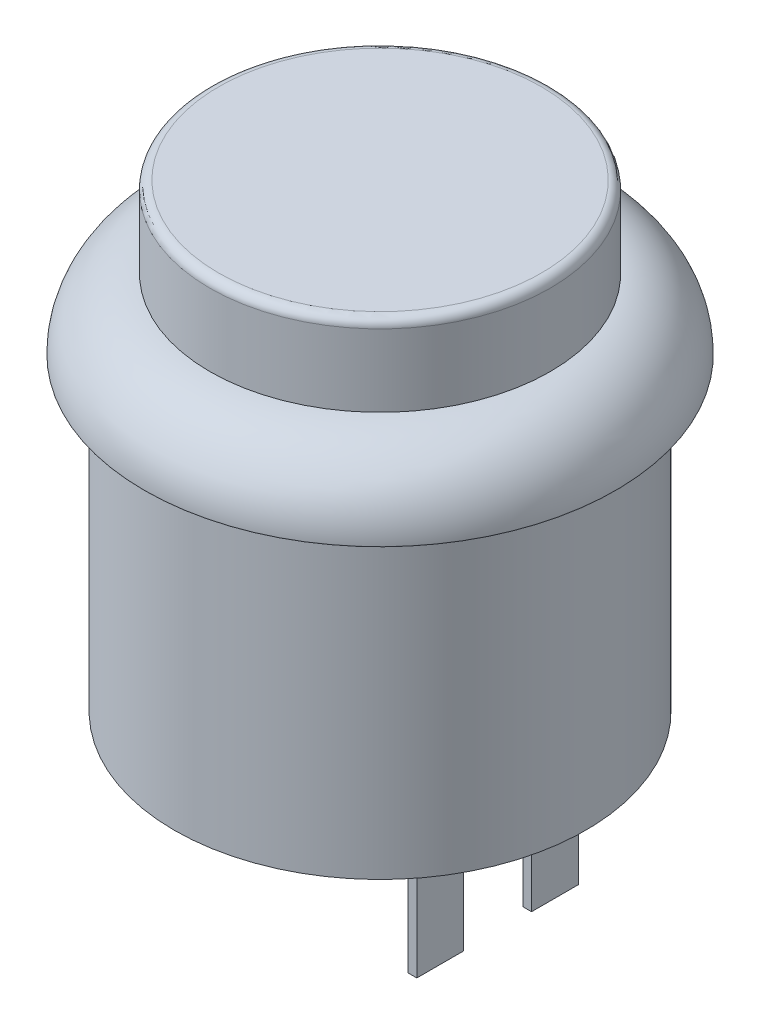
SolidWorks part; units mm, degrees
material "ABS"
ref_plane "Front Plane" through (0, 0, 0) normal (0, 0, 1) x (1, 0, 0)
ref_plane "Top Plane" through (0, 0, 0) normal (0, 1, 0) x (1, 0, 0)
ref_plane "Right Plane" through (0, 0, 0) normal (1, 0, 0) x (0, 0, -1)
sketch "Sketch1" plane through (0, 0, 0) normal (0, 1, 0) x (1, 0, 0)
  circle A0 centre (0, 0) radius 11.735
  dimension "D1" = 23.47
extrude "Boss-Extrude1" add sketch "Sketch1" along normal blind 17.64
sketch "Sketch2" plane through (0, 17.64, 0) normal (0, 1, 0) x (1, 0, 0)
  circle A0 centre (0, 0) radius 13.44
  dimension "D1" = 26.88
extrude "Boss-Extrude2" add sketch "Sketch2" along normal blind 4
sketch "Sketch3" plane through (0, 21.64, 0) normal (0, 1, 0) x (1, 0, 0)
  circle A0 centre (0, 0) radius 9.705
  dimension "D1" = 19.41
extrude "Boss-Extrude3" add sketch "Sketch3" along normal blind 4.62
fillet "Fillet1" radius 4 1 edges at (0, 21.64, 13.44)
fillet "Fillet2" radius 0.5 1 edges at (0, 26.26, 9.705)
sketch "Sketch4" plane through (0, 0, 0) normal (0, -1, 0) x (1, 0, 0)
  line L0 (0, 11.735) -> (0, -11.735) construction
  line L1 (-11.735, 0) -> (11.735, 0) construction
  line L2 (6.2, 4.605) -> (6.7, 4.605)
  line L3 (6.2, 4.605) -> (6.2, 1.935)
  line L4 (6.2, 1.935) -> (6.7, 1.935)
  line L5 (6.7, 4.605) -> (6.7, 1.935)
  line L6 (6.2, -1.94) -> (6.7, -1.94)
  line L7 (6.2, -1.94) -> (6.2, -4.61)
  line L8 (6.2, -4.61) -> (6.7, -4.61)
  line L9 (6.7, -1.94) -> (6.7, -4.61)
  circle A0 centre (0, 0) radius 11.735 construction
  circle A1 centre (0, 0) radius 11.735 construction
  point P19 (6.4086, -2.5072)
  dimension "D1" = 0.5
  dimension "D2" = 0.5
  dimension "D3" = 2.67
  dimension "D4" = 2.67
  dimension "D5" = 1.94
  dimension "D6" = 1.935
  dimension "D7" = 6.2
  dimension "D8" = 6.2
extrude "Boss-Extrude4" add sketch "Sketch4" along normal blind 7.51
